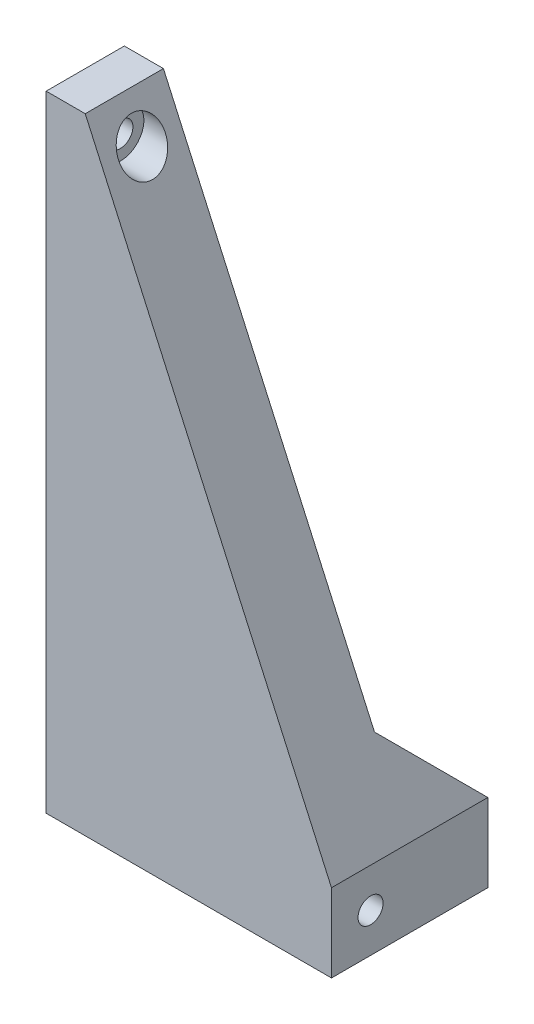
SolidWorks part; units mm, degrees
ref_plane "Front Plane" through (0, 0, 0) normal (0, 0, 1) x (1, 0, 0)
ref_plane "Top Plane" through (0, 0, 0) normal (0, 1, 0) x (1, 0, 0)
ref_plane "Right Plane" through (0, 0, 0) normal (1, 0, 0) x (0, 0, -1)
sketch "ｽｹｯﾁ1" plane through (0, 0, 0) normal (0, 0, 1) x (1, 0, 0)
  line L0 (0, 0) -> (0, 80)
  line L1 (0, 80) -> (5, 80)
  line L2 (5, 80) -> (36.5, 10)
  line L3 (36.5, 10) -> (36.5, 0)
  line L4 (36.5, 0) -> (0, 0)
  dimension "D1" = 36.5
  dimension "D2" = 80
  dimension "D3" = 5
  dimension "D4" = 10
extrude "ﾎﾞｽ - 押し出し1" add sketch "ｽｹｯﾁ1" along normal blind 10
sketch "ｽｹｯﾁ2" plane through (0, 0, 0) normal (0, 0, -1) x (-1, 0, 0)
  line L1 (-36.5, 10) -> (0, 10)
  line L2 (-36.5, 10) -> (-36.5, 0)
  line L3 (-36.5, 0) -> (0, 0)
  line L4 (0, 10) -> (0, 0)
extrude "ﾎﾞｽ - 押し出し2" add sketch "ｽｹｯﾁ2" along normal blind 10
chamfer "面取り1" distance 10 angle 45 1 edges at (18.25, 10, 0)
sketch "ｽｹｯﾁ3" plane through (36.5, 0, 0) normal (1, 0, 0) x (0, 0, -1)
  line L0 (0, 80) -> (0, 20) construction
  line L1 (-10, 0) -> (-10, 10) construction
  line L3 (-10, 0) -> (10, 0) construction
  line L4 (-10, 80) -> (0, 80) construction
  circle A0 centre (-5, 5) radius 1.6
  circle A1 centre (-5, 75) radius 1.6
  dimension "D1" = 3.2
  dimension "D2" = 5
  dimension "D3" = 3.2
  dimension "D5" = 5
  dimension "D8" = 5
  dimension "D4" = 5
extrude "ｶｯﾄ - 押し出し1" cut sketch "ｽｹｯﾁ3" against normal through all
sketch "ｽｹｯﾁ4" plane through (0, 0, 0) normal (0, -1, 0) x (-1, 0, 0)
  line L0 (-36.5, -10) -> (-36.5, 10) construction
  line L1 (-36.5, 10) -> (0, 10) construction
  circle A0 centre (-28.9, 5) radius 1.6
  dimension "D1" = 3.2
  dimension "D2" = 7.6
  dimension "D3" = 5
extrude "ｶｯﾄ - 押し出し2" cut sketch "ｽｹｯﾁ4" against normal through all
sketch "ｽｹｯﾁ5" plane through (36.5, 0, 0) normal (1, 0, 0) x (0, 0, -1)
  circle A0 centre (-5, 75) radius 3
  dimension "D1" = 6
extrude "ｶｯﾄ - 押し出し3" cut sketch "ｽｹｯﾁ5" against normal blind 32
sketch "ｽｹｯﾁ6" plane through (0, 80, 0) normal (0, 1, 0) x (1, 0, 0)
  circle A0 centre (28.9, 5) radius 3
  dimension "D1" = 6
extrude "ｶｯﾄ - 押し出し4" cut sketch "ｽｹｯﾁ6" against normal blind 67
